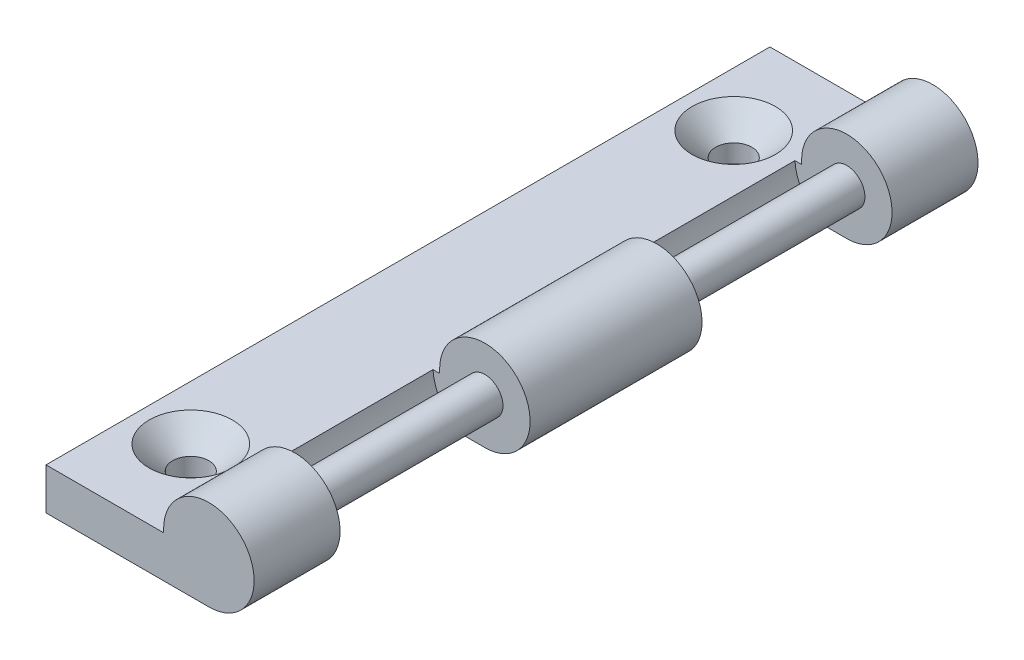
SolidWorks part; units mm, degrees
ref_plane "Front Plane" through (0, 0, 0) normal (0, 0, 1) x (1, 0, 0)
ref_plane "Top Plane" through (0, 0, 0) normal (0, 1, 0) x (1, 0, 0)
ref_plane "Right Plane" through (0, 0, 0) normal (1, 0, 0) x (0, 0, -1)
sketch "Sketch1" plane through (0, 0, 0) normal (0, 1, 0) x (1, 0, 0)
  line L1 (-9, 40) -> (0, 40)
  line L2 (-9, 40) -> (-9, 0)
  line L3 (-9, 0) -> (0, 0)
  line L4 (0, 40) -> (0, 0)
  dimension "D1" = 40
  dimension "D2" = 9
extrude "Boss-Extrude1" add sketch "Sketch1" along normal blind 2.5
sketch "Sketch2" plane through (0, 0, 0) normal (0, 0, 1) x (1, 0, 0)
  circle A0 centre (0, 2.5) radius 2.5
extrude "Boss-Extrude2" add sketch "Sketch2" against normal up to surface (40 mm away) up to face at (-4.5, 1.25, -40)
sketch "Sketch3" plane through (0, 0, 0) normal (0, 0, 1) x (1, 0, 0)
  circle A1 centre (0, 2.5) radius 2.875
  dimension "D1" = 5.75
extrude "Cut-Extrude1" cut sketch "Sketch3" against normal blind 10.5 from offset 4.75 offset against normal yes
ref_plane "Plane1" through (0, 0, -20) normal (0, 0, 1) x (1, 0, 0)
mirror "Mirror1" about plane through (0, 0, -20) normal (0, 0, 1) of "Cut-Extrude1"
sketch "Sketch4" plane through (0, 0, -15.25) normal (0, 0, 1) x (1, 0, 0)
  circle A0 centre (0, 2.5) radius 1
  dimension "D1" = 2
extrude "Boss-Extrude3" add sketch "Sketch4" along normal up to next
mirror "Mirror2" about plane through (0, 0, -20) normal (0, 0, 1) of "Boss-Extrude3"
sketch "Sketch5" plane through (0, 2.5, 0) normal (0, 1, 0) x (1, 0, 0)
  line L0 (-9, 0) -> (-2.5, 0) construction
  line L1 (-9, 40) -> (-9, 0) construction
  circle A0 centre (-6, 5) radius 1
  dimension "D1" = 2
  dimension "D2" = 5
  dimension "D3" = 3
extrude "Cut-Extrude2" cut sketch "Sketch5" against normal through all
mirror "Mirror3" about plane through (0, 0, -20) normal (0, 0, 1) of "Cut-Extrude2"
chamfer "Chamfer1" distance 1.5 angle 45 1 edges at (-6, 2.5, -4)
chamfer "Chamfer2" distance 1.5 angle 45 1 edges at (-6, 2.5, -36)
sketch "Sketch6" plane through (0, 0, 0) normal (0, 0, 1) x (1, 0, 0)
  line L3 (-9, 2.5) -> (-2.5, 2.5)
  line L4 (-9, 2.5) -> (-9, 2.3)
  line L5 (-9, 2.3) -> (-2.5, 2.3)
  line L6 (-2.5, 2.5) -> (-2.5, 2.3)
  point P0 (-2.5, 2.5)
  dimension "D1" = 0.2
extrude "Cut-Extrude3" cut sketch "Sketch6" against normal through all
